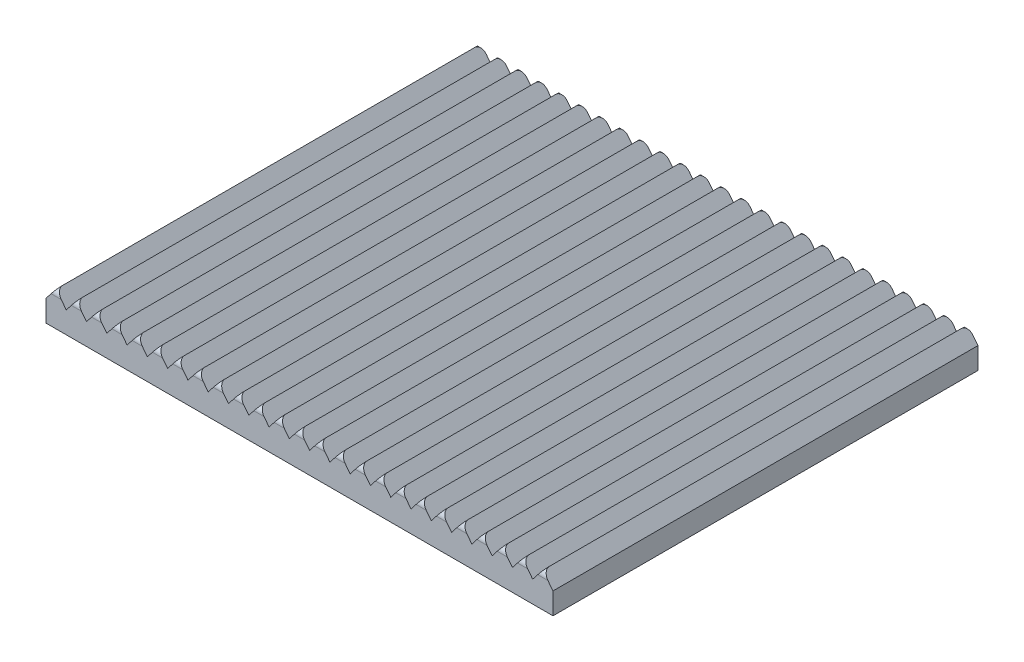
SolidWorks part; units mm, degrees
ref_plane "Front Plane" through (0, 0, 0) normal (0, 0, 1) x (1, 0, 0)
ref_plane "Top Plane" through (0, 0, 0) normal (0, 1, 0) x (1, 0, 0)
ref_plane "Right Plane" through (0, 0, 0) normal (1, 0, 0) x (0, 0, -1)
sketch "Sketch1" plane through (0, 0, 0) normal (0, 1, 0) x (1, 0, 0)
  line L6 (-29.375, 24.625) -> (29.375, 24.625)
  line L28 (-29.375, 24.625) -> (-29.375, -24.625)
  line L29 (-29.375, -24.625) -> (29.375, -24.625)
  line L30 (29.375, 24.625) -> (29.375, -24.625)
  line L31 (-29.375, 24.625) -> (29.375, -24.625) construction
  line L32 (-29.375, -24.625) -> (29.375, 24.625) construction
  circle A1 centre (0, 0) radius 3.05
  point P0 (0, 0)
  dimension "D3" = 6.1
  dimension "D1" = 58.75
  dimension "D2" = 49.25
extrude "Boss-Extrude1" add sketch "Sketch1" along normal blind 1.5
sketch "Sketch2" plane through (0, 0, -24.625) normal (0, 0, -1) x (-1, 0, 0)
  line L0 (-29.375, 1.5) -> (-29.375, 0) construction
  line L1 (-29.375, 1.5) -> (29.375, 1.5)
  line L2 (-29.375, 1.5) -> (-29.375, 2.5)
  line L4 (29.375, 1.5) -> (29.375, 2.5)
  line L5 (-1.175, 2.5) -> (0, 4)
  line L6 (0, 55) -> (0, -55) construction
  line L7 (1.175, 2.5) -> (0, 4)
  line L8 (1.175, 2.5) -> (2.35, 4)
  line L9 (3.525, 2.5) -> (2.35, 4)
  line L10 (3.525, 2.5) -> (4.7, 4)
  line L11 (5.875, 2.5) -> (4.7, 4)
  line L12 (5.875, 2.5) -> (7.05, 4)
  line L13 (8.225, 2.5) -> (7.05, 4)
  line L14 (8.225, 2.5) -> (9.4, 4)
  line L15 (10.575, 2.5) -> (9.4, 4)
  line L16 (10.575, 2.5) -> (11.75, 4)
  line L17 (12.925, 2.5) -> (11.75, 4)
  line L18 (12.925, 2.5) -> (14.1, 4)
  line L19 (15.275, 2.5) -> (14.1, 4)
  line L20 (15.275, 2.5) -> (16.45, 4)
  line L21 (17.625, 2.5) -> (16.45, 4)
  line L22 (17.625, 2.5) -> (18.8, 4)
  line L23 (19.975, 2.5) -> (18.8, 4)
  line L24 (19.975, 2.5) -> (21.15, 4)
  line L25 (22.325, 2.5) -> (21.15, 4)
  line L26 (22.325, 2.5) -> (23.5, 4)
  line L27 (24.675, 2.5) -> (23.5, 4)
  line L28 (24.675, 2.5) -> (25.85, 4)
  line L29 (27.025, 2.5) -> (25.85, 4)
  line L30 (27.025, 2.5) -> (28.2, 4)
  line L31 (29.375, 2.5) -> (28.2, 4)
  line L32 (-29.375, 2.5) -> (-28.2, 4)
  line L33 (-27.025, 2.5) -> (-28.2, 4)
  line L34 (-27.025, 2.5) -> (-25.85, 4)
  line L35 (-24.675, 2.5) -> (-25.85, 4)
  line L36 (-24.675, 2.5) -> (-23.5, 4)
  line L37 (-22.325, 2.5) -> (-23.5, 4)
  line L38 (-22.325, 2.5) -> (-21.15, 4)
  line L39 (-19.975, 2.5) -> (-21.15, 4)
  line L40 (-19.975, 2.5) -> (-18.8, 4)
  line L41 (-17.625, 2.5) -> (-18.8, 4)
  line L42 (-17.625, 2.5) -> (-16.45, 4)
  line L43 (-15.275, 2.5) -> (-16.45, 4)
  line L44 (-15.275, 2.5) -> (-14.1, 4)
  line L45 (-12.925, 2.5) -> (-14.1, 4)
  line L46 (-12.925, 2.5) -> (-11.75, 4)
  line L47 (-10.575, 2.5) -> (-11.75, 4)
  line L48 (-10.575, 2.5) -> (-9.4, 4)
  line L49 (-8.225, 2.5) -> (-9.4, 4)
  line L50 (-8.225, 2.5) -> (-7.05, 4)
  line L51 (-5.875, 2.5) -> (-7.05, 4)
  line L52 (-5.875, 2.5) -> (-4.7, 4)
  line L53 (-3.525, 2.5) -> (-4.7, 4)
  line L54 (-3.525, 2.5) -> (-2.35, 4)
  line L55 (-1.175, 2.5) -> (-2.35, 4)
  dimension "D1" = 1
  dimension "D2" = 1.5
  dimension "D3" = 13
extrude "Boss-Extrude2" add sketch "Sketch2" against normal up to surface (49.25 mm away) up to face at (0, 0.75, 24.625)
sketch "Sketch3" plane through (0, 0, 0) normal (0, -1, 0) x (-1, 0, 0)
  line L0 (0, 2.2) -> (0, -2.2) construction
  line L2 (-1.75, -2.498) -> (-1.75, -5)
  line L3 (-1.75, -5) -> (1.75, -5)
  line L4 (1.75, -2.498) -> (1.75, -5)
  arc A0 (1.75, -2.498) -> (-1.75, -2.498) centre (0, 0) ccw
  dimension "D2" = 6.1
  dimension "D1" = 3.5
  dimension "D3" = 5
  dimension "D4" = 1.75
extrude "Cut-Extrude1" cut sketch "Sketch3" against normal blind 1
sketch "Sketch4" plane through (29.375, 0, 0) normal (1, 0, 0) x (0, 0, -1)
  line L1 (-24.625, 4) -> (-24.625, 2.5) construction
  line L2 (-24.625, 4) -> (24.625, 4) construction
  line L3 (-23.875, 4) -> (-24.625, 4)
  line L4 (-24.625, 4) -> (-24.625, 3.25)
  arc A0 (-24.625, 3.25) -> (-23.875, 4) centre (-23.875, 3.25) cw
extrude "Cut-Extrude3" cut sketch "Sketch4" against normal through all
mirror "Mirror1" about plane through (0, 0, 0) normal (0, 0, 1) of "Cut-Extrude3"
sketch "Sketch5" plane through (0, 1.5, 0) normal (0, -1, 0) x (1, 0, 0)
  circle A0 centre (0, 0) radius 3.1
extrude "Boss-Extrude3" add sketch "Sketch5" along normal blind 0.5
sketch "Sketch6" plane through (0, 1, 0) normal (0, -1, 0) x (1, 0, 0)
  line L1 (1.75, 5) -> (-1.75, 5)
  line L2 (1.75, 5) -> (1.75, 2.498)
  line L3 (1.75, 2.498) -> (-1.75, 2.498)
  line L4 (-1.75, 5) -> (-1.75, 2.498)
  point P6 (0, 0)
  point P7 (-1.75, 2.5588)
  point P9 (0, 0)
  point P10 (-1.75, 2.498)
extrude "Cut-Extrude4" cut sketch "Sketch6" against normal blind 0.5
chamfer "Chamfer3" distance 1.5 angle 45 1 edges at (0, 0, 5)
